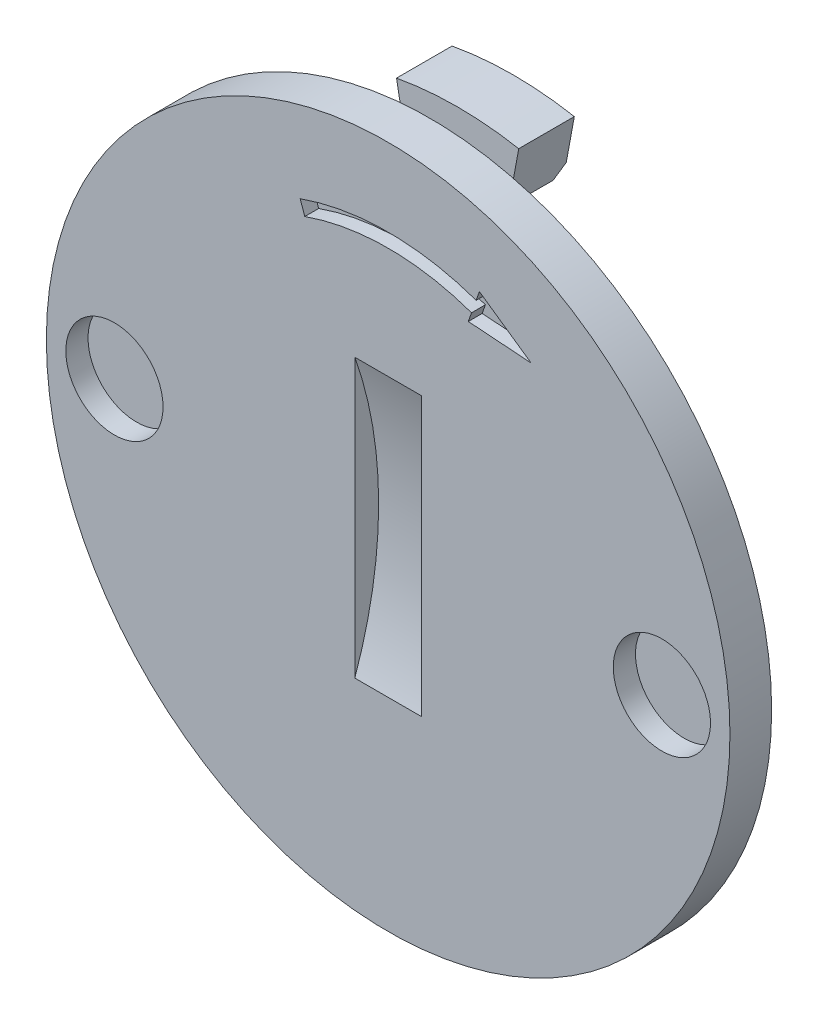
SolidWorks part; units mm, degrees
material "ABS"
ref_plane "Přední rovina" through (0, 0, 0) normal (0, 0, 1) x (1, 0, 0)
ref_plane "Vrchní rovina" through (0, 0, 0) normal (0, 1, 0) x (1, 0, 0)
ref_plane "Pravá rovina" through (0, 0, 0) normal (1, 0, 0) x (0, 0, -1)
sketch "Skica1" plane through (0, 0, 0) normal (0, 0, 1) x (1, 0, 0)
  line L0 (-18.6957, 0) -> (18.043, 0) construction
  line L1 (0, 13.3601) -> (0, -13.2981) construction
  line L2 (-2, 10.8675) -> (-1.8371, 9.9824)
  line L3 (2, 10.8675) -> (1.8371, 9.9824)
  circle A0 centre (0, 0) radius 12.3
  circle A1 centre (-9.85, 0) radius 1.75
  circle A2 centre (9.85, 0) radius 1.75
  arc A5 (2, 10.8675) -> (-2, 10.8675) centre (0, 0) ccw
  arc A6 (1.8371, 9.9824) -> (-1.8371, 9.9824) centre (0, 0) ccw
  dimension "D1" = 24.6
  dimension "D2" = 3.5
  dimension "D3" = 0.7
  dimension "D4" = 10.15
  dimension "D5" = 11.05
  dimension "D6" = 0.9
  dimension "D7" = 4
extrude "Přidat vysunutím1" add sketch "Skica1" along normal blind 1.5 contours A0 A2 A1 L3 A6 L2 A5 | A6 L3 A5 L2 | A2 | A1 region at (0, 10.5479, 0) region at (0, -0.0809, 0) region at (-9.85, 0, 0) region at (9.85, 0, 0)
extrude "Odebrat vysunutím3" cut sketch "Skica1<6>" against normal blind 0.8 from surface contours A1 | A2 region at (-9.85, 0, 0) region at (9.85, 0, 0) starting at face at (12.3, 0, 1.5)
sketch "Skica1<6>" plane through (0, 0, 0) normal (0, 0, 1) x (1, 0, 0) same geometry as "Skica1"
extrude "Přidat vysunutím3" add sketch "Skica1<5>" against normal blind 3 contours A6 L3 A5 L2 region at (0, 10.5479, 0)
sketch "Skica1<5>" plane through (0, 0, 0) normal (0, 0, 1) x (1, 0, 0) same geometry as "Skica1"
sketch "Skica2" plane through (0, 0, 0) normal (0, 0, -1) x (-1, 0, 0)
  line L5 (-2, 10.8675) -> (-2.1991, 11.9493)
  line L6 (2, 10.8675) -> (2.1991, 11.9493)
  arc A2 (2, 10.8675) -> (-2, 10.8675) centre (0, 0) ccw construction
  arc A3 (2, 10.8675) -> (-2, 10.8675) centre (0, 0) ccw
  arc A4 (2.1991, 11.9493) -> (-2.1991, 11.9493) centre (0, 0) ccw
  dimension "D2" = 1.1
extrude "Přidat vysunutím4" add sketch "Skica2" along normal up to surface (3 mm away) from offset 1 up to face at (0, 10.5125, -3)
chamfer "Zkosení1" distance 0.4 angle 45 1 edges at (0, 10.15, -3)
pattern_circular "Kruhové pole1" count 2 over 360 about axis through (0, 0, 0) along (0, 0, 1) of "Zkosení1", "Přidat vysunutím3", "Přidat vysunutím4"
sketch "Skica3" plane through (0, 0, 1.5) normal (0, 0, 1) x (1, 0, 0)
  line L0 (-3.1667, 8.9567) -> (-3, 8.4853)
  line L1 (3.1667, 8.9567) -> (3.2833, 9.2867)
  line L2 (3.2833, 9.2867) -> (5.1441, 7.9924)
  line L3 (5.1441, 7.9924) -> (2.8833, 8.1553)
  line L4 (2.8833, 8.1553) -> (3, 8.4853)
  line L5 (0, 13.8307) -> (0, -1.1643) construction
  arc A0 (3, 8.4853) -> (-3, 8.4853) centre (0, 0) ccw
  arc A1 (3.1667, 8.9567) -> (-3.1667, 8.9567) centre (0, 0) ccw
  dimension "D1" = 9
  dimension "D2" = 9.5
  dimension "D3" = 3
  dimension "D4" = 2.2
  dimension "D5" = 1.2
extrude "Odebrat vysunutím2" cut sketch "Skica3" against normal blind 0.5
sketch "Skica4" plane through (0, 0, 0) normal (1, 0, 0) x (0, 0, -1)
  line L0 (-1.5, 5) -> (-1.5, -5)
  line L1 (-1.5, 12.3) -> (-1.5, -12.3) construction
  arc A0 (-1.5, -5) -> (-1.5, 5) centre (-15.6421, 0) ccw
  dimension "D1" = 30
  dimension "D2" = 10
extrude "Odebrat vysunutím1" cut sketch "Skica4" against normal blind 1.2 and the other way blind 1.2
